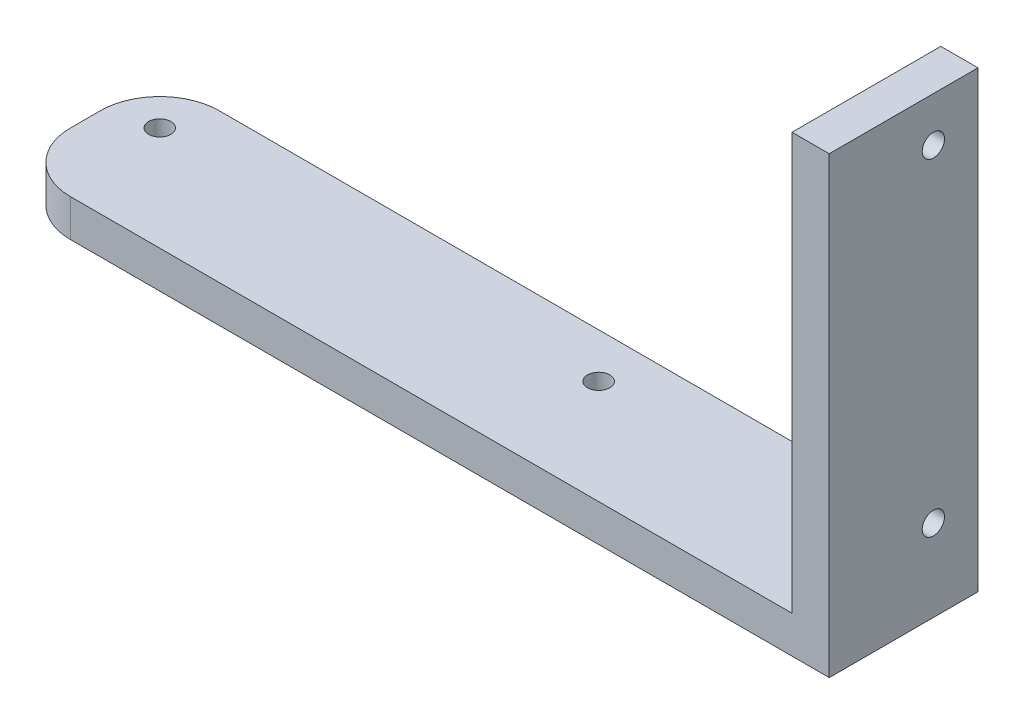
SolidWorks part; units mm, degrees
ref_plane "Front Plane" through (0, 0, 0) normal (0, 0, 1) x (1, 0, 0)
ref_plane "Top Plane" through (0, 0, 0) normal (0, 1, 0) x (1, 0, 0)
ref_plane "Right Plane" through (0, 0, 0) normal (1, 0, 0) x (0, 0, -1)
sketch "Sketch1" plane through (0, 0, 0) normal (0, 1, 0) x (1, 0, 0)
  line L1 (0, 0) -> (110, 0)
  line L2 (0, 0) -> (0, 20)
  line L3 (0, 20) -> (110, 20)
  line L4 (110, 0) -> (110, 20)
  dimension "D1" = 110
  dimension "D2" = 20
extrude "Boss-Extrude1" add sketch "Sketch1" along normal blind 5
sketch "Sketch2" plane through (0, 5, 0) normal (0, 1, 0) x (1, 0, 0)
  line L0 (110, 20) -> (0, 20) construction
  line L1 (110, 0) -> (105, 0)
  line L2 (110, 0) -> (110, 20)
  line L3 (110, 20) -> (105, 20)
  line L4 (105, 0) -> (105, 20)
  dimension "D1" = 5
extrude "Boss-Extrude2" add sketch "Sketch2" along normal blind 56
sketch "Sketch3" plane through (0, 5, 0) normal (0, 1, 0) x (1, 0, 0)
  line L0 (0, 20) -> (0, 0) construction
  line L2 (105, 20) -> (0, 20) construction
  circle A0 centre (6, 14) radius 1.5
  circle A1 centre (65, 14) radius 1.5
  dimension "D1" = 3
  dimension "D2" = 6
  dimension "D3" = 6
  dimension "D4" = 59
extrude "Cut-Extrude1" cut sketch "Sketch3" against normal through all
fillet "Fillet1" radius 8 2 edges at (0, 2.5, 0) (0, 2.5, -20)
sketch "Sketch4" plane through (105, 0, 0) normal (-1, 0, 0) x (0, 0, 1)
  line L1 (-20, 5) -> (0, 5) construction
  line L4 (-20, 61) -> (-20, 5) construction
  circle A0 centre (-14, 11) radius 1.5
  circle A2 centre (-14, 55) radius 1.5
  dimension "D1" = 6
  dimension "D2" = 3
  dimension "D3" = 6
  dimension "D4" = 44
extrude "Cut-Extrude2" cut sketch "Sketch4" against normal through all
